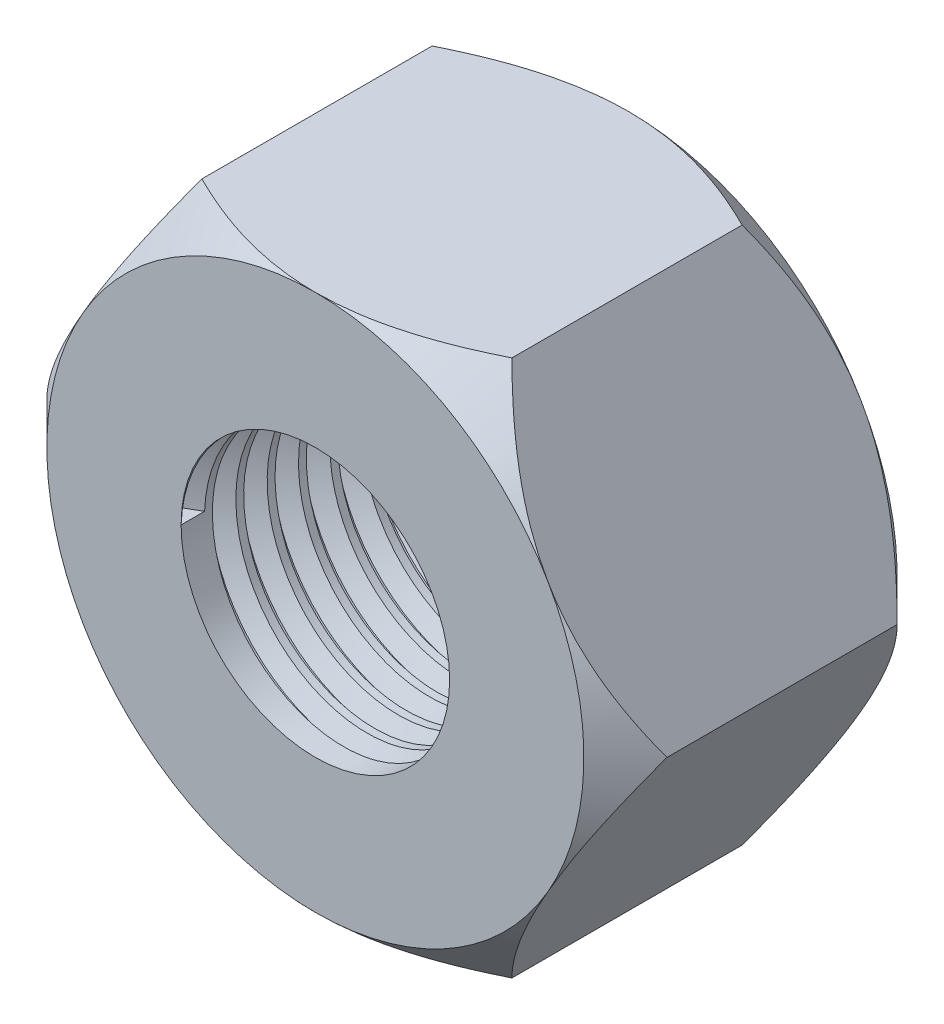
SolidWorks part; units mm, degrees
ref_plane "Front Plane" through (0, 0, 0) normal (0, 0, 1) x (1, 0, 0)
ref_plane "Top Plane" through (0, 0, 0) normal (0, 1, 0) x (1, 0, 0)
ref_plane "Right Plane" through (0, 0, 0) normal (1, 0, 0) x (0, 0, -1)
sketch "Sketch1" plane through (0, 0, 0) normal (0, 0, 1) x (1, 0, 0)
  line L1 (34.641, 0) -> (17.3205, 30)
  line L2 (17.3205, 30) -> (-17.3205, 30)
  line L3 (-17.3205, 30) -> (-34.641, 0)
  line L4 (-34.641, 0) -> (-17.3205, -30)
  line L5 (-17.3205, -30) -> (17.3205, -30)
  line L6 (17.3205, -30) -> (34.641, 0)
  circle A0 centre (0, 0) radius 15
  circle A1 centre (0, 0) radius 30 construction
  dimension "D1" = 60
  dimension "D2" = 30
extrude "Boss-Extrude1" add sketch "Sketch1" along normal mid plane 35
sketch "Sketch2" plane through (0, 0, 17.5) normal (0, 0, 1) x (1, 0, 0)
  circle A0 centre (0, 0) radius 30
extrude "Cut-Extrude1" cut sketch "Sketch2" against normal blind 35 draft 45 flip side to cut
mirror "Mirror1" about plane through (0, 0, 0) normal (0, 0, 1) of "Cut-Extrude1"
thread "Thread1" pitch 3.5 method cut profile "Thread Profile1" start angle 0, offset 0, length 0, pitch 3.5, diameter 30
ref_plane "Plane1" through (-15, 0, 17.5) normal (0, -1, 0) x (-1, 0, 0)
sketch "Thread Profile1" plane through (-15, 0, 17.5) normal (0, -1, 0) x (-1, 0, 0)
  line L0 (0, 0) -> (0, 3.5) construction
  line L1 (0, 0) -> (1.8944, 1.0937)
  line L2 (1.8944, 1.0937) -> (1.8944, 1.5312)
  line L3 (1.8944, 1.5312) -> (0, 2.625)
  line L4 (1.8944, 1.3125) -> (0, 1.3125) construction
  line L11 (0, 0) -> (0, 2.625)
  point P2 (0, 0)
  dimension "Pitch" = 3.5
  dimension "Profile_Angle" = 60
  dimension "Profile_Land" = 0.4375
  dimension "Profile_Height" = 1.8944
